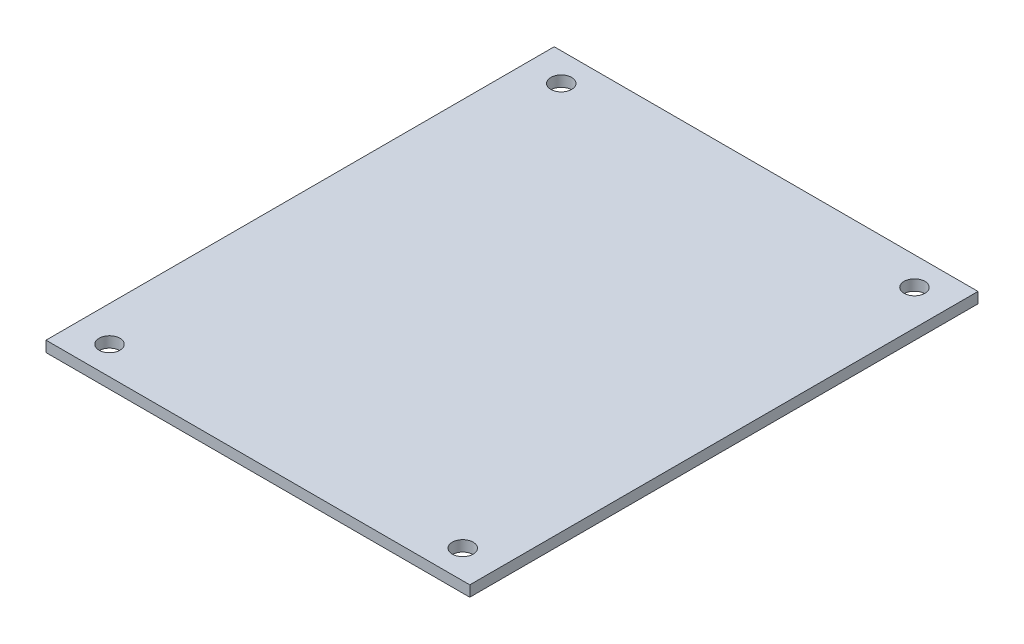
SolidWorks part; units mm, degrees
ref_plane "Płaszczyzna przednia" through (0, 0, 0) normal (0, 0, 1) x (1, 0, 0)
ref_plane "Płaszczyzna górna" through (0, 0, 0) normal (0, 1, 0) x (1, 0, 0)
ref_plane "Płaszczyzna prawa" through (0, 0, 0) normal (1, 0, 0) x (0, 0, -1)
sketch "Szkic1" plane through (0, 0, 0) normal (0, 1, 0) x (1, 0, 0)
  line L1 (30.5, -36.576) -> (-30.5, -36.576)
  line L2 (30.5, -36.576) -> (30.5, 36.576)
  line L3 (30.5, 36.576) -> (-30.5, 36.576)
  line L4 (-30.5, -36.576) -> (-30.5, 36.576)
  line L5 (30.5, -36.576) -> (-30.5, 36.576) construction
  line L6 (30.5, 36.576) -> (-30.5, -36.576) construction
  circle A0 centre (-25.42, 32.512) radius 1.5
  circle A1 centre (25.42, 32.512) radius 1.5
  circle A2 centre (-25.42, -32.512) radius 1.5
  circle A3 centre (25.42, -32.512) radius 1.5
  point P0 (0, 0)
  dimension "D3" = 5.08
  dimension "D5" = 5.08
  dimension "D7" = 4.064
  dimension "D9" = 5.08
  dimension "D1" = 61
  dimension "D2" = 73.152
  dimension "D4" = 4.064
  dimension "D6" = 4.064
  dimension "D8" = 5.08
  dimension "D10" = 4.064
extrude "Dodanie-wyciągnięcie1" add sketch "Szkic1" along normal blind 1.55
